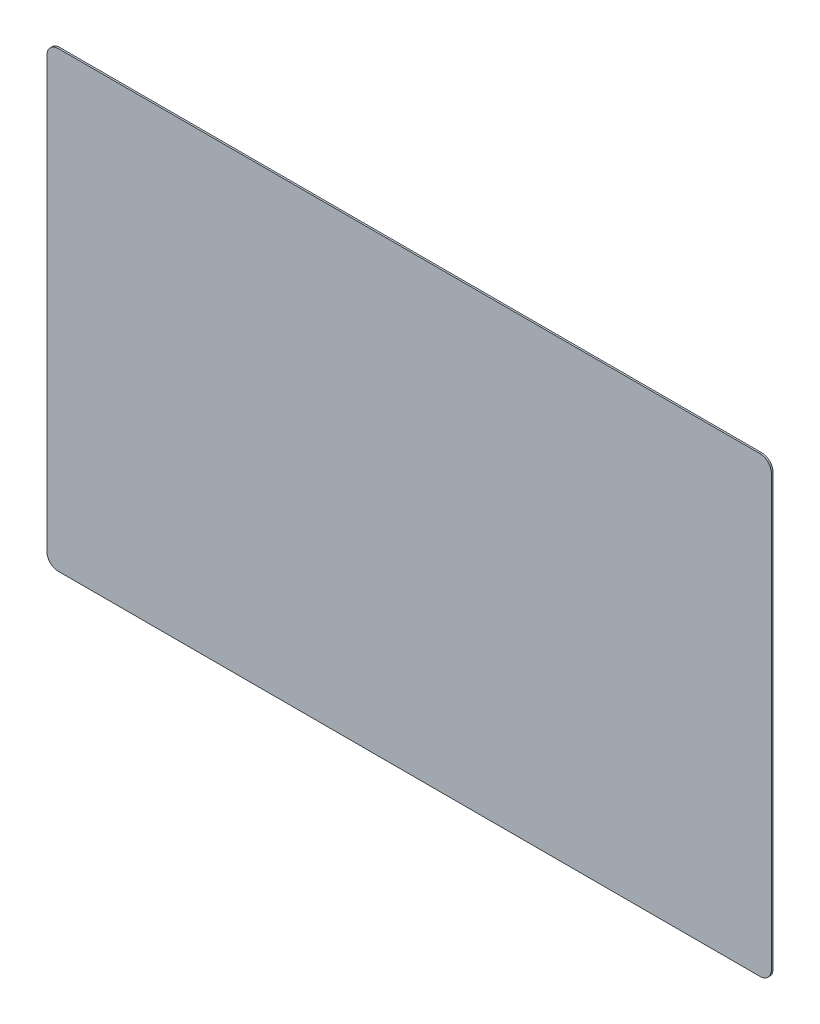
SolidWorks part; units mm, degrees
material "1.0037 (S235JR)"
ref_plane "Front Plane" through (0, 0, 0) normal (0, 0, 1) x (1, 0, 0)
ref_plane "Top Plane" through (0, 0, 0) normal (0, 1, 0) x (1, 0, 0)
ref_plane "Right Plane" through (0, 0, 0) normal (1, 0, 0) x (0, 0, -1)
sketch "Sketch1" plane through (0, 0, 0) normal (0, 0, 1) x (1, 0, 0)
  line L1 (320, -200) -> (-320, -200)
  line L2 (320, -200) -> (320, 200)
  line L3 (320, 200) -> (-320, 200)
  line L4 (-320, -200) -> (-320, 200)
  line L5 (320, -200) -> (-320, 200) construction
  line L6 (320, 200) -> (-320, -200) construction
  point P0 (0, 0)
  dimension "D1" = 640
  dimension "D2" = 400
base flange "Base-Flange1" sketch "Sketch1" thickness 1.5 reverse thickness direction no parameters "D1"=0.7366
fillet "Fillet1" radius 10 4 edges at (320, -200, -0.75) (320, 200, -0.75) (-320, 200, -0.75) (-320, -200, -0.75)
sketch "Bend-Lines1" [suppressed] plane through (0, 0, 0) normal (0, 1, 0) x (1, 0, 0)
sketch "Bounding-Box1" [suppressed] plane through (0, 0, 0) normal (0, 1, 0) x (1, 0, 0)
sheet metal parameters "Sheet-Metal1" thickness 1.5 parameters "D1"=0.7366
flat pattern "Flat-Pattern1" [suppressed]
sketch "Bend-Lines2" plane through (0, 0, 0) normal (0, 1, 0) x (1, 0, 0)
sketch3d "Bounding-Box2" [suppressed]
  line L0 (-320, 200, 0) -> (320, 200, 0) construction
  line L1 (-320, -200, 0) -> (320, -200, 0) construction
  line L2 (-320, 200, 0) -> (-320, -200, 0) construction
  line L3 (320, 200, 0) -> (320, -200, 0) construction
